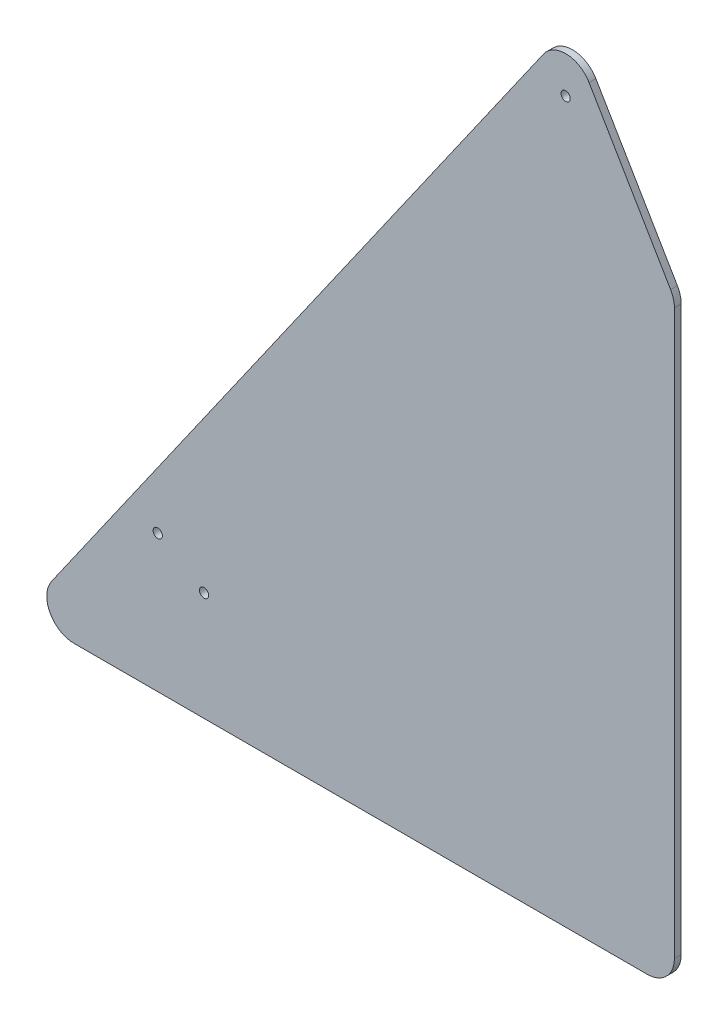
SolidWorks part; units mm, degrees
ref_plane "Front Plane" through (0, 0, 0) normal (0, 0, 1) x (1, 0, 0)
ref_plane "Top Plane" through (0, 0, 0) normal (0, 1, 0) x (1, 0, 0)
ref_plane "Right Plane" through (0, 0, 0) normal (1, 0, 0) x (0, 0, -1)
sketch "Sketch1" plane through (0, 0, 0) normal (0, 0, 1) x (1, 0, 0)
  line L0 (0, 0) -> (304.8, 0)
  line L1 (304.8, 0) -> (304.8, 279.4)
  line L2 (254.9547, 364.1131) -> (0, 0)
  line L3 (304.8, 279.4) -> (254.9547, 364.1131)
  dimension "D1" = 304.8
  dimension "D2" = 279.4
  dimension "D3" = 55
  dimension "D4" = 444.5
extrude "Boss-Extrude1" add sketch "Sketch1" along normal blind 3.175
sketch "Sketch2" plane through (0, 0, 3.175) normal (0, 0, 1) x (1, 0, 0)
  line L0 (254.9547, 364.1131) -> (0, 0) construction
  line L1 (0, 0) -> (304.8, 0) construction
  circle A0 centre (63.5, 64.1173) radius 2.159
  circle A1 centre (254, 336.1795) radius 2.159
  circle A2 centre (85.1289, 50.8) radius 2.159
  point P11 (-0.1432, 0.3994)
  dimension "D3" = 4.318
  dimension "D5" = 4.318
  dimension "D9" = 4.318
  dimension "D1" = 63.5
  dimension "D2" = 15.24
  dimension "D4" = 254
  dimension "D6" = 15.24
  dimension "D7" = 25.4
  dimension "D8" = 50.8
extrude "Cut-Extrude1" cut sketch "Sketch2" against normal through all
fillet "Fillet1" radius 12.7 4 edges at (0, 0, 1.5875) (304.8, 0, 1.5875) (304.8, 279.4, 1.5875) (254.9547, 364.1131, 1.5875)
equation "\"D6@Sketch2\"=\"D2@Sketch2\""
